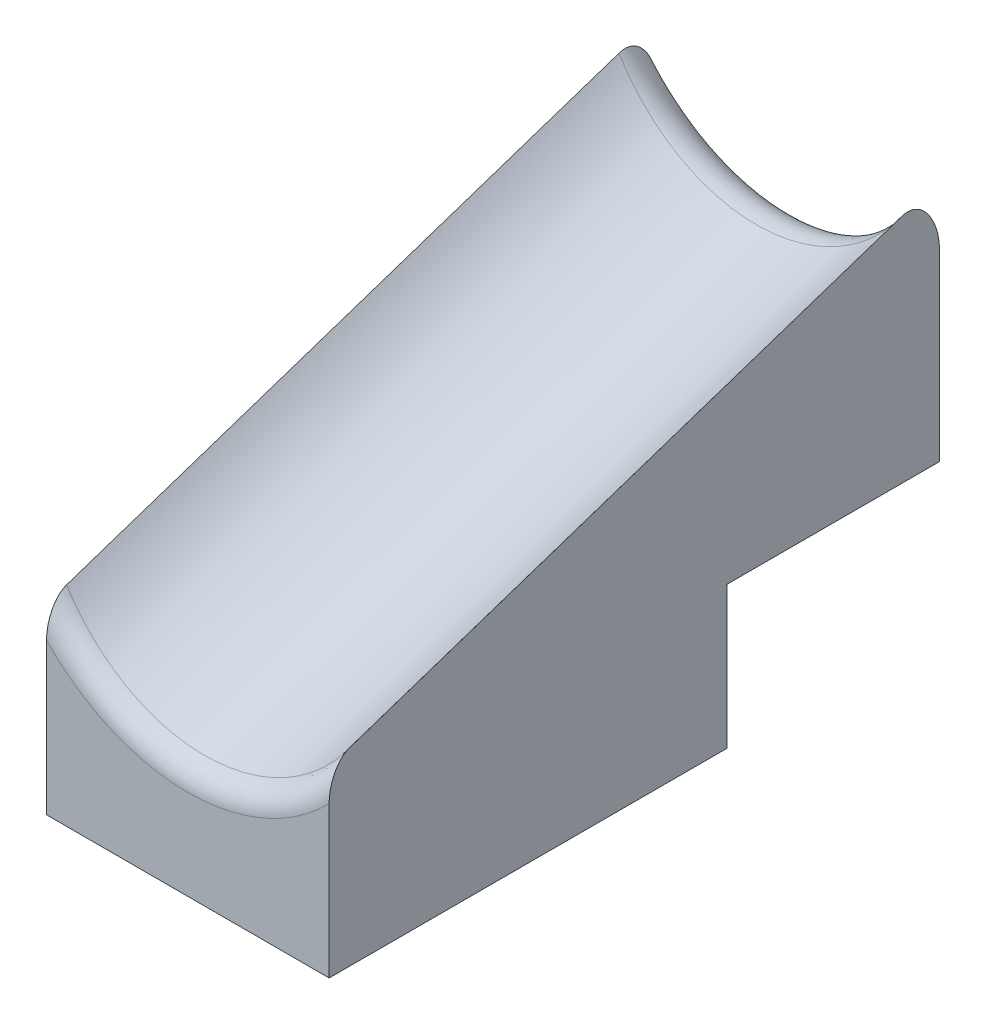
SolidWorks part; units mm, degrees
ref_plane "Front Plane" through (0, 0, 0) normal (0, 0, 1) x (1, 0, 0)
ref_plane "Top Plane" through (0, 0, 0) normal (0, 1, 0) x (1, 0, 0)
ref_plane "Right Plane" through (0, 0, 0) normal (1, 0, 0) x (0, 0, -1)
sketch "Sketch1" plane through (0, 0, 0) normal (0, 1, 0) x (1, 0, 0)
  line L1 (0, 0) -> (101.6, 0)
  line L2 (0, 0) -> (0, -304.8)
  line L3 (0, -304.8) -> (101.6, -304.8)
  line L4 (101.6, 0) -> (101.6, -304.8)
  dimension "D1" = 101.6
  dimension "D2" = 304.8
extrude "Boss-Extrude1" add sketch "Sketch1" along normal blind 101.6
sketch "Sketch3" plane through (101.6, 0, 0) normal (1, 0, 0) x (0, 0, -1)
  line L0 (-304.8, 0) -> (0, 101.6)
  line L1 (0, 101.6) -> (-304.8, 101.6)
  line L2 (-304.8, 101.6) -> (-304.8, 0)
extrude "Cut-Extrude1" cut sketch "Sketch3" against normal blind 101.6
ref_plane "Plane1" through (0, 10.16, -30.48) normal (0, 0.3162, -0.9487) x (-1, 0, 0)
sketch "Sketch4" plane through (0, 10.16, -30.48) normal (0, 0.3162, -0.9487) x (-1, 0, 0)
  line L2 (-101.6, 96.3862) -> (0, 96.3862) construction
  line L3 (0, 96.3862) -> (0, 0) construction
  circle A0 centre (-50.8, 134.4862) radius 63.5
  dimension "D1" = 127
  dimension "D2" = 38.1
  dimension "D3" = 50.8
extrude "Cut-Extrude2" cut sketch "Sketch4" against normal blind 508
sketch "Sketch7" plane through (101.6, 0, 0) normal (1, 0, 0) x (0, 0, -1)
  line L0 (-304.8, 0) -> (0, 0) construction
  line L1 (-21.79, 0) -> (-8.636, 0)
  line L2 (-21.79, 0) -> (-21.79, 13.97)
  line L3 (-21.79, 13.97) -> (-8.636, 13.97)
  line L4 (-8.636, 0) -> (-8.636, 13.97)
  line L5 (0, 101.6) -> (0, 0) construction
  dimension "D1" = 13.154
  dimension "D2" = 8.636
  dimension "D3" = 13.97
extrude "Cut-Extrude3" cut sketch "Sketch7" against normal blind 152.4
sketch "Sketch8" plane through (0, 0, 8.636) normal (0, 0, 1) x (1, 0, 0)
  line L0 (0, 0) -> (0, 13.97) construction
  line L1 (101.6, 0) -> (0, 0)
  line L2 (101.6, 0) -> (101.6, 6.985)
  line L3 (101.6, 6.985) -> (0, 6.985)
  line L4 (0, 0) -> (0, 6.985)
extrude "Boss-Extrude2" add sketch "Sketch8" along normal blind 6.35
chamfer "Chamfer1" distance 6.731 angle 60 1 edges at (50.8, 6.985, 14.986) first distance on face at (50.8, 6.985, 11.811)
sketch "Sketch9" plane through (0, 0, 0) normal (0, -1, 0) x (1, 0, 0)
  line L0 (101.6, 21.79) -> (0, 21.79)
  line L1 (101.6, 21.79) -> (101.6, 314.6167)
  line L2 (0, 21.79) -> (0, 314.6167)
  line L3 (101.6, 314.6167) -> (0, 314.6167)
  line L4 (0, 21.79) -> (101.6, 21.79) construction
extrude "Boss-Extrude3" add sketch "Sketch9" along normal blind 12.7
sketch "Sketch10" plane through (0, -12.7, 0) normal (0, -1, 0) x (-1, 0, 0)
  line L0 (-101.6, -314.6167) -> (0, -314.6167)
  line L1 (-101.6, -314.6167) -> (-101.6, -219.3667)
  line L2 (0, -314.6167) -> (0, -219.3667)
  line L3 (-101.6, -219.3667) -> (0, -219.3667)
  line L4 (-101.6, -21.79) -> (-101.6, -314.6167) construction
  line L5 (-101.6, -314.6167) -> (0, -314.6167) construction
  line L6 (0, -314.6167) -> (0, -21.79) construction
  dimension "D1" = 95.25
extrude "Cut-Extrude4" cut sketch "Sketch10" against normal blind 58.42
fillet "Fillet1" radius 8.89 1 edges at (50.8, 1.7038, 219.3667)
fillet "Fillet2" radius 11.43 1 edges at (50.8, 74.826, 0)
sketch "Sketch11" plane through (101.6, 0, 0) normal (1, 0, 0) x (0, 0, -1)
  line L1 (0, 13.97) -> (-76.4, 13.97)
  line L2 (0, 13.97) -> (0, -24.13)
  line L3 (0, -24.13) -> (-76.4, -24.13)
  line L4 (-76.4, 13.97) -> (-76.4, -24.13)
  line L7 (-8.636, 13.97) -> (-21.79, 13.97) construction
  line L8 (0, 79.8909) -> (0, 0) construction
  dimension "D1" = 0
  dimension "D2" = 76.4
  dimension "D3" = 0
  dimension "D4" = 38.1
extrude "Cut-Extrude5" cut sketch "Sketch11" against normal blind 101.6
sketch "Sketch12" plane through (0, 13.97, 0) normal (0, -1, 0) x (1, 0, 0)
  line L0 (50.8, 0) -> (50.8, 76.4) construction
  line L1 (0, 0) -> (101.6, 0) construction
  line L2 (0, 76.4) -> (101.6, 76.4) construction
  circle A0 centre (50.8, 25.4) radius 19.05
  point P7 (50.8, 51.05)
  point P8 (50.8, 26.6433)
  point P9 (0, 0)
  dimension "D2" = 38.1
  dimension "D1" = 25.4
extrude "Boss-Extrude4" add sketch "Sketch12" along normal blind 25.4
sketch "Sketch14" plane through (0, -12.7, 0) normal (0, -1, 0) x (1, 0, 0)
  line L0 (0, 219.3667) -> (0, 76.4) construction
  line L1 (0, 76.4) -> (101.6, 76.4)
  line L2 (0, 76.4) -> (0, 219.3667)
  line L3 (0, 219.3667) -> (101.6, 219.3667)
  line L4 (101.6, 76.4) -> (101.6, 219.3667)
  line L5 (0, 219.3667) -> (101.6, 219.3667) construction
  line L6 (101.6, 76.4) -> (101.6, 219.3667) construction
  line L7 (101.6, 76.4) -> (0, 76.4) construction
  dimension "D1" = 0
extrude "Boss-Extrude5" add sketch "Sketch14" along normal blind 24.384
